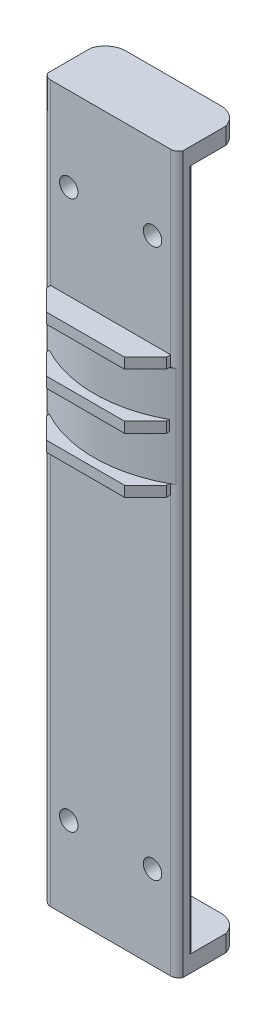
SolidWorks part; units mm, degrees
material "PETG"
ref_plane "Płaszczyzna przednia" through (0, 0, 0) normal (0, 0, 1) x (1, 0, 0)
ref_plane "Płaszczyzna górna" through (0, 0, 0) normal (0, 1, 0) x (1, 0, 0)
ref_plane "Płaszczyzna prawa" through (0, 0, 0) normal (1, 0, 0) x (0, 0, -1)
sketch "Sketch1" plane through (0, 0, 0) normal (0, 1, 0) x (1, 0, 0)
  line L0 (-19.2094, 16) -> (19.2094, 16)
  arc A0 (19.2094, 16) -> (-19.2094, 16) centre (0, 0) ccw
  dimension "D1" = 50
  dimension "D2" = 16
extrude "Boss-Extrude1" add sketch "Sketch1" along normal blind 163
fillet "Fillet1" radius 2 2 edges at (-19.2094, 81.5, -16) (19.2094, 81.5, -16)
sketch "Sketch2" plane through (0, 163, 0) normal (0, 1, 0) x (1, 0, 0)
  line L0 (-16.3178, 31) -> (-16.3178, 18)
  line L1 (-14.3178, 16) -> (14.3178, 16)
  line L2 (-14.3178, 16) -> (14.3178, 16)
  line L3 (16.3178, 18) -> (16.3178, 31)
  line L4 (-16.3178, 31) -> (16.3178, 31)
  arc A3 (15.5628, 19.5652) -> (-15.5628, 19.5652) centre (0, 0) ccw
  arc A4 (-15.5628, 19.5652) -> (-14.3178, 16) centre (-14.3178, 18) ccw
  arc A5 (14.3178, 16) -> (15.5628, 19.5652) centre (14.3178, 18) ccw
  arc A7 (-16.3178, 18) -> (-14.3178, 16) centre (-14.3178, 18) ccw
  arc A8 (14.3178, 16) -> (16.3178, 18) centre (14.3178, 18) ccw
  dimension "D2" = 15
  dimension "D1" = 0
extrude "Boss-Extrude3" add sketch "Sketch2" along normal blind 4
extrude "Boss-Extrude4" add sketch "Sketch2<2>" against normal blind 4 from surface starting at face at (0, 0, -18.9203)
sketch "Sketch2<2>" plane through (0, 163, 0) normal (0, 1, 0) x (1, 0, 0) same geometry as "Sketch2"
fillet "Fillet2" radius 5 4 edges at (-16.3178, -2, -31) (16.3178, -2, -31) (16.3178, 165, -31) (-16.3178, 165, -31)
sketch "Sketch3" plane through (0, -4, 0) normal (0, -1, 0) x (1, 0, 0)
  line L4 (-16.3178, -18) -> (-16.3178, -26)
  line L5 (-11.3178, -31) -> (11.3178, -31)
  line L6 (16.3178, -26) -> (16.3178, -18)
  line L7 (14.3178, -16) -> (-14.3178, -16)
  line L8 (-16.3178, -18) -> (-16.3178, -26)
  line L9 (-11.3178, -31) -> (11.3178, -31)
  line L10 (16.3178, -26) -> (16.3178, -18)
  line L11 (14.3178, -16) -> (-14.3178, -16)
  arc A0 (15.3405, -16.2813) -> (-15.3405, -16.2813) centre (0, -42.0624) ccw
  arc A7 (-16.3178, -26) -> (-11.3178, -31) centre (-11.3178, -26) ccw
  arc A8 (11.3178, -31) -> (16.3178, -26) centre (11.3178, -26) ccw
  arc A9 (16.3178, -18) -> (14.3178, -16) centre (14.3178, -18) ccw
  arc A10 (-14.3178, -16) -> (-16.3178, -18) centre (-14.3178, -18) ccw
  arc A11 (-16.3178, -26) -> (-11.3178, -31) centre (-11.3178, -26) ccw
  arc A12 (11.3178, -31) -> (16.3178, -26) centre (11.3178, -26) ccw
  arc A13 (16.3178, -18) -> (14.3178, -16) centre (14.3178, -18) ccw
  arc A14 (-14.3178, -16) -> (-16.3178, -18) centre (-14.3178, -18) ccw
  arc M15 (16.3178, -18) -> (14.3178, -16) centre (14.3178, -18) ccw
  line M16 (14.3178, -16) -> (-14.3178, -16)
  arc M17 (-14.3178, -16) -> (-16.3178, -18) centre (-14.3178, -18) ccw
  dimension "D1" = 60
  dimension "D2" = 0
extrude "Boss-Extrude5" add sketch "Sketch3" against normal blind 24 from offset 102 contours A0 M15 M17 M16 region at (0, -4, -14.4168) offset against normal yes
sketch "Sketch4" plane through (0, 122, 0) normal (0, 1, 0) x (1, 0, 0)
  line L0 (14.3178, 16) -> (-14.3178, 16) construction
  line L1 (-14.3178, 16) -> (14.3178, 16)
  line L2 (-14.3178, 16) -> (-14.3178, 10)
  line L3 (-14.3178, 10) -> (14.3178, 10)
  line L4 (14.3178, 16) -> (14.3178, 10)
  dimension "D1" = 6
extrude "Boss-Extrude6" add sketch "Sketch4" along normal blind 2.5
extrude "Boss-Extrude7" add sketch "Sketch4<2>" against normal blind 2.5 from surface starting at face at (0, 98, -15.0514)
sketch "Sketch4<2>" plane through (0, 122, 0) normal (0, 1, 0) x (1, 0, 0) same geometry as "Sketch4"
extrude "Boss-Extrude8" add sketch "Sketch4<3>" along normal blind 1.25 and the other way blind 1.25 from offset 12 offset against normal yes
sketch "Sketch4<3>" plane through (0, 122, 0) normal (0, 1, 0) x (1, 0, 0) same geometry as "Sketch4"
chamfer "Chamfer1" distance 5 angle 45 6 edges at (14.3178, 96.75, -10) (14.3178, 110, -10) (14.3178, 123.25, -10) (-14.3178, 96.75, -10) (-14.3178, 110, -10) (-14.3178, 123.25, -10)
hole_wizard "Ø4.4 (4.4) Diameter Hole1" positions "Sketch5" profile "Sketch6" hole size "Ø4.4" standard "DIN" end condition through all
sketch "Sketch5" plane through (0, 0, -16) normal (0, 0, 1) x (1, 0, 0)
  line L0 (-14.3178, 167) -> (14.3178, 167) construction
  line L2 (-14.3178, -4) -> (14.3178, -4) construction
  line L3 (-10, 147) -> (10, 147) construction
  line L5 (0, 167) -> (0, 147) construction
  point P0 (-10, 147)
  point P4 (10, 147)
  point P5 (10, 16)
  point P6 (-10, 16)
  dimension "D3" = 20
  dimension "D4" = 20
  dimension "D5" = 20
  dimension "D1" = 2
  dimension "D2" = 2
sketch "Sketch6" plane through (-10, 147, -16) normal (1, 0, 0) x (0, -1, 0)
  line L0 (0, 0) -> (0, 15)
  line L1 (0, 15) -> (2.2, 15)
  line L2 (2.2, 15) -> (2.2, 0)
  line L5 (2.2, 0) -> (0, 0)
  line L11 (0, -6.35) -> (0, 107.95) construction
  dimension "Thru Hole Dia." = 4.4
  dimension "Thru Hole Depth" = 15
sketch "Sketch7" plane through (-16.3178, 0, 0) normal (-1, 0, 0) x (0, 0, 1)
  line L1 (-38.5007, 169.3898) -> (-10.7635, 169.3898)
  line L2 (-38.5007, 169.3898) -> (-38.5007, -9.487)
  line L3 (-38.5007, -9.487) -> (-10.7635, -9.487)
  line L4 (-10.7635, 169.3898) -> (-10.7635, -9.487)
extrude "Cut-Extrude1" cut sketch "Sketch7" against normal blind 0.2
extrude "Cut-Extrude2" cut sketch "Sketch7<2>" along normal blind 0.2 from surface starting at face at (16.3178, 165, -22)
sketch "Sketch7<2>" plane through (-16.3178, 0, 0) normal (-1, 0, 0) x (0, 0, 1) same geometry as "Sketch7"
